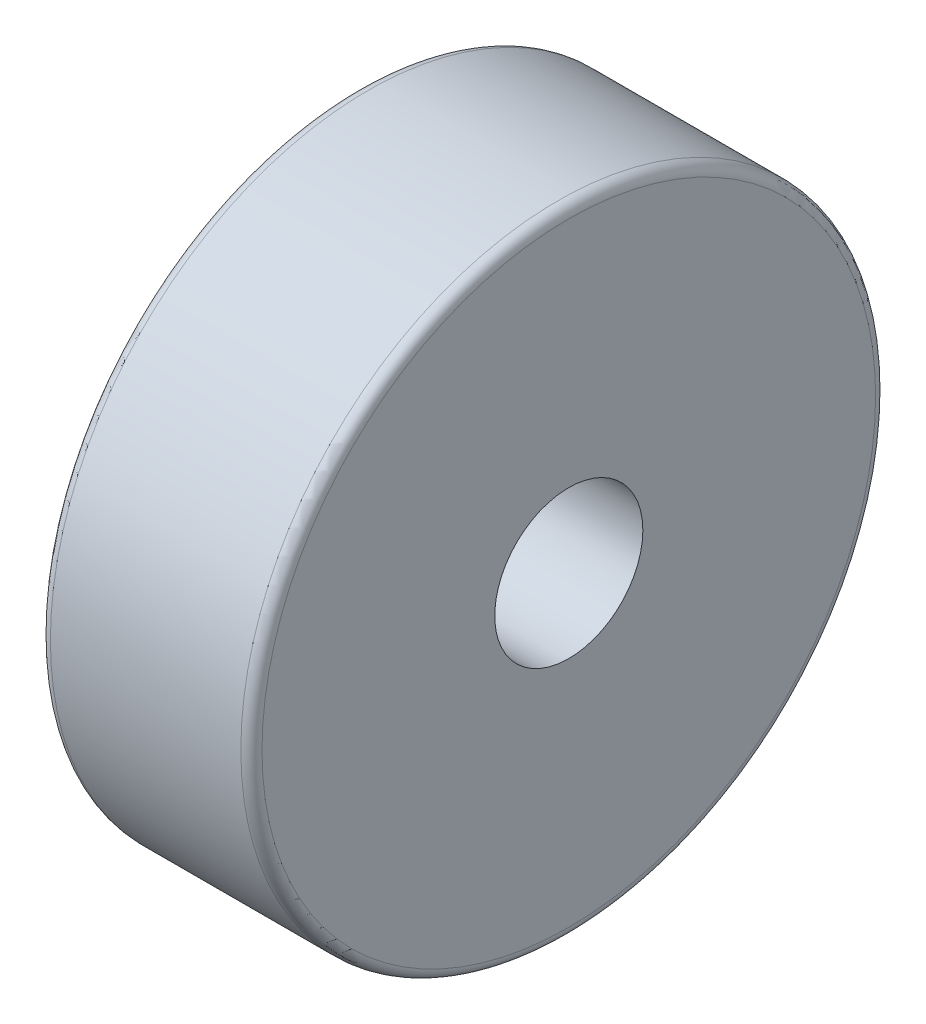
SolidWorks part; units mm, degrees
material "1060 Alloy"
ref_plane "Front Plane" through (0, 0, 0) normal (0, 0, 1) x (1, 0, 0)
ref_plane "Top Plane" through (0, 0, 0) normal (0, 1, 0) x (1, 0, 0)
ref_plane "Right Plane" through (0, 0, 0) normal (1, 0, 0) x (0, 0, -1)
sketch "Sketch2" plane through (0, 0, 0) normal (1, 0, 0) x (0, 0, -1)
  circle A0 centre (0, 0) radius 150
  dimension "D1" = 300
extrude "Boss-Extrude2" add sketch "Sketch2" along normal blind 100 separate body
sketch "Sketch1" plane through (100, 0, 0) normal (1, 0, 0) x (0, 0, -1)
  circle A0 centre (0, 0) radius 35
  dimension "D1" = 70
extrude "Boss-Extrude1" add sketch "Sketch1" along normal blind 60
fillet "Fillet1" radius 5 2 edges at (0, 0, -150) (100, 0, -150)
sketch "Sketch7" plane through (0, 0, 0) normal (-1, 0, 0) x (0, 0, 1)
  line L0 (0, 158.5437) -> (0, -186.44) construction
  line L1 (0, -33) -> (0, 33) construction
  line L2 (-173.4217, 0) -> (182.7205, 0) construction
  line L3 (88, 0) -> (-88, 0) construction
  line L4 (-20, 128.4523) -> (-20, 20)
  line L5 (-128.4523, 20) -> (-20, 20)
  arc A0 (-20, 128.4523) -> (-128.4523, 20) centre (0, 0) ccw
  dimension "D1" = 260
  dimension "D2" = 20
  dimension "D3" = 20
extrude "Cut-Extrude4" cut sketch "Sketch7" against normal blind 30
ref_axis "Axis2" through (88.9581, 0, 0) along (-1, 0, 0)
pattern_circular "CirPattern2" count 4 over 360 about axis through (88.9581, 0, 0) along (-1, 0, 0) of "Cut-Extrude4"
sketch "Sketch8" plane through (160, 0, 0) normal (1, 0, 0) x (0, 0, -1)
  circle A1 centre (0, 0) radius 35
  circle A2 centre (0, 0) radius 35
  dimension "D2" = 70
  dimension "D1" = 0
extrude "Cut-Extrude5" cut sketch "Sketch8" against normal through all
sketch "Sketch9" plane through (0, 0, 0) normal (-1, 0, 0) x (0, 0, 1)
  circle A0 centre (0, 0) radius 50
  dimension "D1" = 100
extrude "Cut-Extrude6" cut sketch "Sketch9" against normal up to surface (30 mm away) up to face at (30, 53.815, -53.815)
